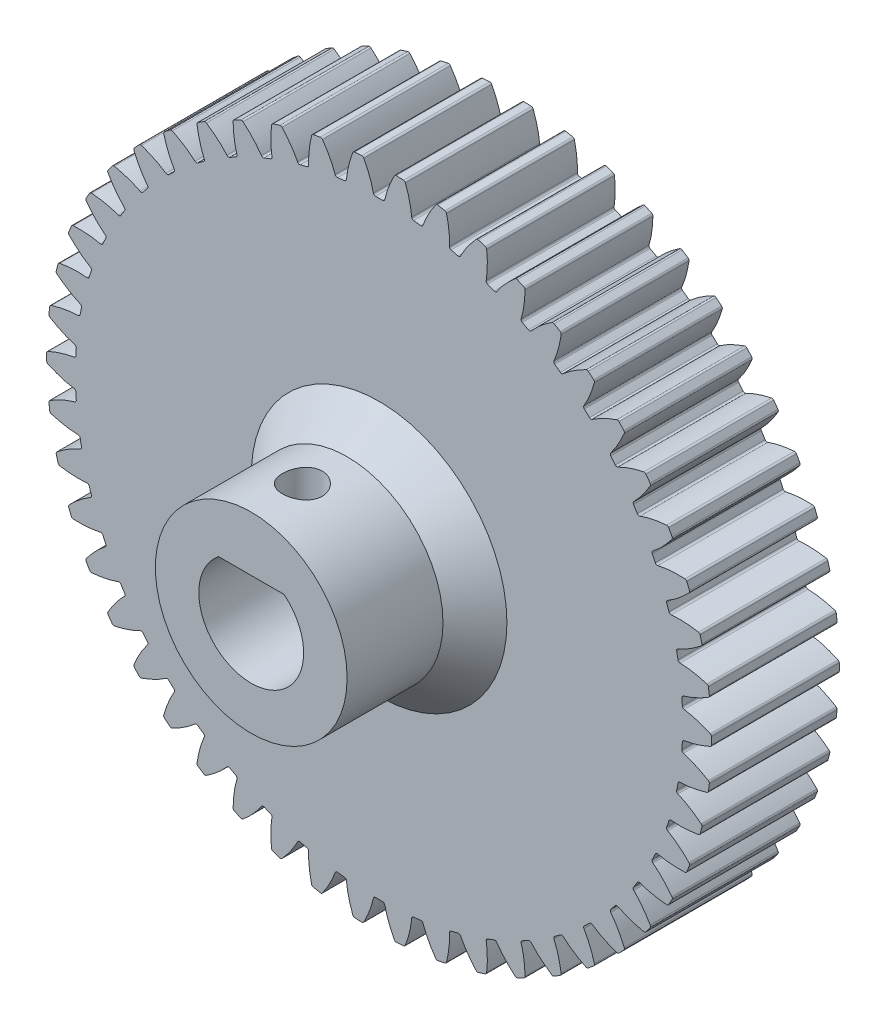
SolidWorks part; units mm, degrees
material "Alloy Steel"
ref_plane "Front" through (0, 0, 0) normal (0, 0, 1) x (1, 0, 0)
ref_plane "Top" through (0, 0, 0) normal (0, 1, 0) x (1, 0, 0)
ref_plane "Right" through (0, 0, 0) normal (1, 0, 0) x (0, 0, -1)
sketch "Sketch1" plane through (0, 0, 0) normal (0, 0, 1) x (1, 0, 0)
  circle A0 centre (0, 0) radius 26
  dimension "OutsideDiameter" = 52
extrude "Boss-Extrude1" add sketch "Sketch1" along normal blind 10
sketch "Sketch3" plane through (0, 0, 0) normal (0, 0, 1) x (1, 0, 0)
  line L0 (0, 0) -> (43.7181, 0) construction
  line L2 (0, 0) -> (-0.3921, 23.7468) construction
  line L3 (0, 0) -> (0.3921, 23.7468) construction
  line L4 (0.3921, 23.7468) -> (0.3879, 23.4891) construction
  line L5 (0, 0) -> (0, 61.276) construction
  line L6 (-0.3921, 23.7468) -> (-0.3879, 23.4891) construction
  circle A0 centre (0, 0) radius 26 construction
  circle A1 centre (0, 0) radius 25 construction
  circle A2 centre (0, 0) radius 23.4923 construction
  arc A3 (0.3921, 23.7468) -> (-0.3921, 23.7468) centre (0, 0) ccw construction
  arc A5 (1.2454, 25.9702) -> (-1.2454, 25.9702) centre (0, 0) ccw
  spline S0 degree 4 poles (-0.3879, 23.4891) (-0.388, 23.493) (-0.3884, 23.504) (-0.3897, 23.5247) (-0.3924, 23.5584) (-0.3969, 23.6014) (-0.4038, 23.6569) (-0.4135, 23.7223) (-0.4257, 23.7941) (-0.4406, 23.8721) (-0.4569, 23.9499) (-0.4746, 24.0275) (-0.4935, 24.1047) (-0.5179, 24.1981) (-0.5491, 24.3101) (-0.5886, 24.4407) (-0.6369, 24.5888) (-0.6899, 24.7394) (-0.7452, 24.8875) (-0.8046, 25.0368) (-0.8646, 25.1811) (-0.9305, 25.3308) (-0.9933, 25.4688) (-1.0677, 25.6231) (-1.1289, 25.7476) (-1.2139, 25.9114) (-1.2654, 26.008) (-1.3272, 26.121) (-1.3555, 26.1712) (-1.3728, 26.202) knots 0 0 0 0 0 0.005377 0.015084 0.028532 0.04661 0.064855 0.092111 0.119476 0.146842 0.174209 0.201575 0.228941 0.256307 0.307035 0.361767 0.4165 0.471232 0.525964 0.580697 0.635429 0.690161 0.744894 0.799626 0.854358 0.909091 0.954545 1 1 1 1 1 construction
  spline S1 degree 4 poles (-0.3879, 23.4891) (-0.388, 23.493) (-0.3884, 23.504) (-0.3897, 23.5247) (-0.3924, 23.5584) (-0.3969, 23.6014) (-0.4038, 23.6569) (-0.4135, 23.7223) (-0.4257, 23.7941) (-0.4406, 23.8721) (-0.4569, 23.9499) (-0.4746, 24.0275) (-0.4935, 24.1047) (-0.5179, 24.1981) (-0.5491, 24.3101) (-0.5886, 24.4407) (-0.6369, 24.5888) (-0.6899, 24.7394) (-0.7452, 24.8875) (-0.8046, 25.0368) (-0.8646, 25.1811) (-0.9305, 25.3308) (-0.9933, 25.4688) (-1.0677, 25.6231) (-1.1289, 25.7476) (-1.1955, 25.8759) (-1.2284, 25.9383) (-1.2454, 25.9702) knots 0 0 0 0 0 0.005377 0.015084 0.028532 0.04661 0.064855 0.092111 0.119476 0.146842 0.174209 0.201575 0.228941 0.256307 0.307035 0.361767 0.4165 0.471232 0.525964 0.580697 0.635429 0.690161 0.744894 0.799626 0.854358 0.909091 0.909091 0.909091 0.909091 0.909091
  spline S2 degree 4 poles (0.3879, 23.4891) (0.388, 23.493) (0.3884, 23.504) (0.3897, 23.5247) (0.3924, 23.5584) (0.3969, 23.6014) (0.4038, 23.6569) (0.4135, 23.7223) (0.4257, 23.7941) (0.4406, 23.8721) (0.4569, 23.9499) (0.4746, 24.0275) (0.4935, 24.1047) (0.5179, 24.1981) (0.5491, 24.3101) (0.5886, 24.4407) (0.6369, 24.5888) (0.6899, 24.7394) (0.7452, 24.8875) (0.8046, 25.0368) (0.8646, 25.1811) (0.9305, 25.3308) (0.9933, 25.4688) (1.0677, 25.6231) (1.1289, 25.7476) (1.2139, 25.9114) (1.2654, 26.008) (1.3272, 26.121) (1.3555, 26.1712) (1.3728, 26.202) knots 0 0 0 0 0 0.005377 0.015084 0.028532 0.04661 0.064855 0.092111 0.119476 0.146842 0.174209 0.201575 0.228941 0.256307 0.307035 0.361767 0.4165 0.471232 0.525964 0.580697 0.635429 0.690161 0.744894 0.799626 0.854358 0.909091 0.954545 1 1 1 1 1 construction
  spline S3 degree 4 poles (0.3879, 23.4891) (0.388, 23.493) (0.3884, 23.504) (0.3897, 23.5247) (0.3924, 23.5584) (0.3969, 23.6014) (0.4038, 23.6569) (0.4135, 23.7223) (0.4257, 23.7941) (0.4406, 23.8721) (0.4569, 23.9499) (0.4746, 24.0275) (0.4935, 24.1047) (0.5179, 24.1981) (0.5491, 24.3101) (0.5886, 24.4407) (0.6369, 24.5888) (0.6899, 24.7394) (0.7452, 24.8875) (0.8046, 25.0368) (0.8646, 25.1811) (0.9305, 25.3308) (0.9933, 25.4688) (1.0677, 25.6231) (1.1289, 25.7476) (1.1955, 25.8759) (1.2284, 25.9383) (1.2454, 25.9702) knots 0 0 0 0 0 0.005377 0.015084 0.028532 0.04661 0.064855 0.092111 0.119476 0.146842 0.174209 0.201575 0.228941 0.256307 0.307035 0.361767 0.4165 0.471232 0.525964 0.580697 0.635429 0.690161 0.744894 0.799626 0.854358 0.909091 0.909091 0.909091 0.909091 0.909091
  point P0 (0, 23.75)
  dimension "OutsideDiameter" = 52
  dimension "PitchCircle" = 50
  dimension "BaseCircle" = 46.9846
  dimension "DedendumCircle" = 47.5
sketch "DCLTBC" [suppressed] plane through (0, 0, 0) normal (0, 0, 1) x (1, 0, 0)
  line L0 (0, 0) -> (41.04, 0) construction
  line L1 (-0.539, 11.2371) -> (-0.5627, 11.7327) construction
  line L2 (0.539, 11.2371) -> (0.5627, 11.7327) construction
  line L3 (-0.539, 11.2371) -> (-0.5627, 11.7327)
  line L4 (0.539, 11.2371) -> (0.5627, 11.7327)
  line L5 (0, 0) -> (0, 104.9356) construction
  circle A0 centre (0, 0) radius 13.5
  circle A1 centre (0, 0) radius 12.5 construction
  circle A2 centre (0, 0) radius 11.7462 construction
  arc A3 (0.539, 11.2371) -> (-0.539, 11.2371) centre (0, 0) ccw construction
  arc A4 (0.539, 11.2371) -> (-0.539, 11.2371) centre (0, 0) ccw
  spline S0 degree 4 poles (-1995.7925, -124.0386) (-18.637, 9.6549) (-0.7482, 10.902) (-0.5144, 11.3546) (-0.568, 11.7819) (-0.5727, 11.8124) (-0.5797, 11.8517) (-0.5892, 11.8979) (-0.601, 11.9485) (-0.6152, 12.0034) (-0.6307, 12.0579) (-0.6473, 12.1122) (-0.6648, 12.1662) (-0.6873, 12.2313) (-0.716, 12.3091) (-0.752, 12.3996) (-0.7958, 12.5017) (-0.8436, 12.6052) (-0.8931, 12.7065) (-0.9461, 12.8082) (-0.9995, 12.9061) (-1.0579, 13.0071) (-1.1133, 13.1) (-1.1787, 13.2033) (-1.5156, 13.7241) (-2.9947, 15.6922) (22.2491, -20.3107) (-1154.5903, 1647.3833) knots -0.784355 -0.784355 -0.784355 -0.784355 -0.784355 0.005377 0.015084 0.028532 0.04661 0.064855 0.092111 0.119476 0.146842 0.174209 0.201575 0.228941 0.256307 0.307035 0.361767 0.4165 0.471232 0.525964 0.580697 0.635429 0.690161 0.744894 0.799626 0.854358 2.062408 2.062408 2.062408 2.062408 2.062408 only from (-0.5627, 11.7327) to (-1.3344, 13.4339) construction
  spline S1 degree 4 poles (1995.7925, -124.0386) (18.637, 9.6549) (0.7482, 10.902) (0.5144, 11.3546) (0.568, 11.7819) (0.5727, 11.8124) (0.5797, 11.8517) (0.5892, 11.8979) (0.601, 11.9485) (0.6152, 12.0034) (0.6307, 12.0579) (0.6473, 12.1122) (0.6648, 12.1662) (0.6873, 12.2313) (0.716, 12.3091) (0.752, 12.3996) (0.7958, 12.5017) (0.8436, 12.6052) (0.8931, 12.7065) (0.9461, 12.8082) (0.9995, 12.9061) (1.0579, 13.0071) (1.1133, 13.1) (1.1787, 13.2033) (1.5156, 13.7241) (2.9947, 15.6922) (-22.2491, -20.3107) (1154.5903, 1647.3833) knots -0.784355 -0.784355 -0.784355 -0.784355 -0.784355 0.005377 0.015084 0.028532 0.04661 0.064855 0.092111 0.119476 0.146842 0.174209 0.201575 0.228941 0.256307 0.307035 0.361767 0.4165 0.471232 0.525964 0.580697 0.635429 0.690161 0.744894 0.799626 0.854358 2.062408 2.062408 2.062408 2.062408 2.062408 only from (0.5627, 11.7327) to (1.3344, 13.4339) construction
  spline S2 degree 4 poles (-0.5627, 11.7327) (-0.5629, 11.7355) (-0.5635, 11.7432) (-0.565, 11.758) (-0.568, 11.7819) (-0.5727, 11.8124) (-0.5797, 11.8517) (-0.5892, 11.8979) (-0.601, 11.9485) (-0.6152, 12.0034) (-0.6307, 12.0579) (-0.6473, 12.1122) (-0.6648, 12.1662) (-0.6873, 12.2313) (-0.716, 12.3091) (-0.752, 12.3996) (-0.7958, 12.5017) (-0.8436, 12.6052) (-0.8931, 12.7065) (-0.9461, 12.8082) (-0.9995, 12.9061) (-1.0579, 13.0071) (-1.1133, 13.1) (-1.1787, 13.2033) (-1.2325, 13.2864) (-1.2907, 13.3715) (-1.3195, 13.4128) (-1.3344, 13.4339) knots 0 0 0 0 0 0.005377 0.015084 0.028532 0.04661 0.064855 0.092111 0.119476 0.146842 0.174209 0.201575 0.228941 0.256307 0.307035 0.361767 0.4165 0.471232 0.525964 0.580697 0.635429 0.690161 0.744894 0.799626 0.854358 0.909091 0.909091 0.909091 0.909091 0.909091
  spline S3 degree 4 poles (0.5627, 11.7327) (0.5629, 11.7355) (0.5635, 11.7432) (0.565, 11.758) (0.568, 11.7819) (0.5727, 11.8124) (0.5797, 11.8517) (0.5892, 11.8979) (0.601, 11.9485) (0.6152, 12.0034) (0.6307, 12.0579) (0.6473, 12.1122) (0.6648, 12.1662) (0.6873, 12.2313) (0.716, 12.3091) (0.752, 12.3996) (0.7958, 12.5017) (0.8436, 12.6052) (0.8931, 12.7065) (0.9461, 12.8082) (0.9995, 12.9061) (1.0579, 13.0071) (1.1133, 13.1) (1.1787, 13.2033) (1.2325, 13.2864) (1.2907, 13.3715) (1.3195, 13.4128) (1.3344, 13.4339) knots 0 0 0 0 0 0.005377 0.015084 0.028532 0.04661 0.064855 0.092111 0.119476 0.146842 0.174209 0.201575 0.228941 0.256307 0.307035 0.361767 0.4165 0.471232 0.525964 0.580697 0.635429 0.690161 0.744894 0.799626 0.854358 0.909091 0.909091 0.909091 0.909091 0.909091
  dimension "OutsideDiameter" = 52
  dimension "PitchCircle" = 50
  dimension "BaseCircle" = 46.9846
extrude "Cut-Extrude-DCLTBC" [suppressed] cut sketch "DCLTBC" along normal through all
fillet "Fillet-Tip-DCLTBC" [suppressed] radius 0.1678
fillet "Fillet-Root-DCLTBC" [suppressed] radius 0.3355
pattern_circular "CirPattern-DCLTBC" [suppressed] count 50 over 360
sketch "DCGTBC" plane through (0, 0, 0) normal (0, 0, 1) x (1, 0, 0)
  line L0 (0, 0) -> (41.04, 0) construction
  line L1 (-23.6596, 2.0699) -> (0, 0) construction
  line L2 (0, 0) -> (23.6596, 2.0699) construction
  line L3 (0, 0) -> (-16.5124, 0)
  line L5 (0, 0) -> (0, 104.9356) construction
  circle A0 centre (0, 0) radius 26
  circle A1 centre (0, 0) radius 25 construction
  circle A2 centre (0, 0) radius 23.4923 construction
  arc A3 (0.3921, 23.7468) -> (-0.3921, 23.7468) centre (0, 0) ccw construction
  arc A11 (23.6596, 2.0699) -> (-23.6596, 2.0699) centre (0, 0) ccw
  spline S4 degree 4 poles (999.4864, -18.7848) (11.7157, 21.9438) (0.5361, 22.5725) (0.3526, 23.0676) (0.3924, 23.5584) (0.3969, 23.6014) (0.4038, 23.6569) (0.4135, 23.7223) (0.4257, 23.7941) (0.4406, 23.8721) (0.4569, 23.9499) (0.4746, 24.0275) (0.4935, 24.1047) (0.5179, 24.1981) (0.5491, 24.3101) (0.5886, 24.4407) (0.6369, 24.5888) (0.6899, 24.7394) (0.7452, 24.8875) (0.8046, 25.0368) (0.8646, 25.1811) (0.9305, 25.3308) (0.9933, 25.4688) (1.0677, 25.6231) (1.3761, 26.2503) (2.5138, 28.2725) (-11.1356, 2.527) (472.7395, 907.8123) knots -0.631302 -0.631302 -0.631302 -0.631302 -0.631302 0.005377 0.015084 0.028532 0.04661 0.064855 0.092111 0.119476 0.146842 0.174209 0.201575 0.228941 0.256307 0.307035 0.361767 0.4165 0.471232 0.525964 0.580697 0.635429 0.690161 0.744894 0.799626 0.854358 1.793522 1.793522 1.793522 1.793522 1.793522 only from (0.3879, 23.4891) to (1.2454, 25.9702) construction
  spline S5 degree 4 poles (-999.4864, -18.7848) (-11.7157, 21.9438) (-0.5361, 22.5725) (-0.3526, 23.0676) (-0.3924, 23.5584) (-0.3969, 23.6014) (-0.4038, 23.6569) (-0.4135, 23.7223) (-0.4257, 23.7941) (-0.4406, 23.8721) (-0.4569, 23.9499) (-0.4746, 24.0275) (-0.4935, 24.1047) (-0.5179, 24.1981) (-0.5491, 24.3101) (-0.5886, 24.4407) (-0.6369, 24.5888) (-0.6899, 24.7394) (-0.7452, 24.8875) (-0.8046, 25.0368) (-0.8646, 25.1811) (-0.9305, 25.3308) (-0.9933, 25.4688) (-1.0677, 25.6231) (-1.3761, 26.2503) (-2.5138, 28.2725) (11.1356, 2.527) (-472.7395, 907.8123) knots -0.631302 -0.631302 -0.631302 -0.631302 -0.631302 0.005377 0.015084 0.028532 0.04661 0.064855 0.092111 0.119476 0.146842 0.174209 0.201575 0.228941 0.256307 0.307035 0.361767 0.4165 0.471232 0.525964 0.580697 0.635429 0.690161 0.744894 0.799626 0.854358 1.793522 1.793522 1.793522 1.793522 1.793522 only from (-0.3879, 23.4891) to (-1.2454, 25.9702) construction
  spline S6 degree 4 poles (0.3879, 23.4891) (0.388, 23.493) (0.3884, 23.504) (0.3897, 23.5247) (0.3924, 23.5584) (0.3969, 23.6014) (0.4038, 23.6569) (0.4135, 23.7223) (0.4257, 23.7941) (0.4406, 23.8721) (0.4569, 23.9499) (0.4746, 24.0275) (0.4935, 24.1047) (0.5179, 24.1981) (0.5491, 24.3101) (0.5886, 24.4407) (0.6369, 24.5888) (0.6899, 24.7394) (0.7452, 24.8875) (0.8046, 25.0368) (0.8646, 25.1811) (0.9305, 25.3308) (0.9933, 25.4688) (1.0677, 25.6231) (1.1289, 25.7476) (1.1955, 25.8759) (1.2284, 25.9383) (1.2454, 25.9702) knots 0 0 0 0 0 0.005377 0.015084 0.028532 0.04661 0.064855 0.092111 0.119476 0.146842 0.174209 0.201575 0.228941 0.256307 0.307035 0.361767 0.4165 0.471232 0.525964 0.580697 0.635429 0.690161 0.744894 0.799626 0.854358 0.909091 0.909091 0.909091 0.909091 0.909091
  spline S7 degree 4 poles (-0.3879, 23.4891) (-0.388, 23.493) (-0.3884, 23.504) (-0.3897, 23.5247) (-0.3924, 23.5584) (-0.3969, 23.6014) (-0.4038, 23.6569) (-0.4135, 23.7223) (-0.4257, 23.7941) (-0.4406, 23.8721) (-0.4569, 23.9499) (-0.4746, 24.0275) (-0.4935, 24.1047) (-0.5179, 24.1981) (-0.5491, 24.3101) (-0.5886, 24.4407) (-0.6369, 24.5888) (-0.6899, 24.7394) (-0.7452, 24.8875) (-0.8046, 25.0368) (-0.8646, 25.1811) (-0.9305, 25.3308) (-0.9933, 25.4688) (-1.0677, 25.6231) (-1.1289, 25.7476) (-1.1955, 25.8759) (-1.2284, 25.9383) (-1.2454, 25.9702) knots 0 0 0 0 0 0.005377 0.015084 0.028532 0.04661 0.064855 0.092111 0.119476 0.146842 0.174209 0.201575 0.228941 0.256307 0.307035 0.361767 0.4165 0.471232 0.525964 0.580697 0.635429 0.690161 0.744894 0.799626 0.854358 0.909091 0.909091 0.909091 0.909091 0.909091
  dimension "D1" = 5
  dimension "D2" = 5
  dimension "OutsideDiameter" = 52
  dimension "PitchCircle" = 50
  dimension "BaseCircle" = 46.9846
extrude "Cut-Extrude-DCGTBC" cut sketch "DCGTBC" along normal through all
fillet "Fillet-Tip-DCGTBC" radius 0.1678 4 edges at (1.2454, 25.9702, 5) (-1.2454, 25.9702, 5) (0.4177, 23.7463, 5) (-0.4177, 23.7463, 5)
pattern_circular "CirPattern-DCGTBC" count 50 over 360 about axis through (0, 0, 10) along (0, 0, 1) of "Cut-Extrude-DCGTBC", "Fillet-Tip-DCGTBC"
sketch "Sketch6" plane through (0, 0, 0) normal (0, 0, -1) x (-1, 0, 0)
  line L0 (-2.5627, 3.2004) -> (2.5627, 3.2004)
  arc A0 (-2.5627, 3.2004) -> (2.5627, 3.2004) centre (0, 0) ccw
  dimension "D1" = 8.2
  dimension "D2" = 3.2004
extrude "Cut-Extrude1" cut sketch "Sketch6" against normal through all both and the other way through all
sketch "Sketch7" plane through (0, 0, 0) normal (0, 0, -1) x (-1, 0, 0)
  circle A0 centre (0, 0) radius 25
  dimension "D1" = 50
sketch "Sketch8" plane through (0, 0, 10) normal (0, 0, 1) x (1, 0, 0)
  circle A0 centre (0, 0) radius 25
  dimension "D1" = 50
sketch "Sketch9" plane through (0, 0, 10) normal (0, 0, 1) x (1, 0, 0)
  line L0 (-2.5627, 3.2004) -> (2.5627, 3.2004) construction
  line L1 (-2.5627, 3.2004) -> (2.5627, 3.2004)
  arc A0 (-2.5627, 3.2004) -> (2.5627, 3.2004) centre (0, 0) ccw construction
  arc A1 (-2.5627, 3.2004) -> (2.5627, 3.2004) centre (0, 0) ccw
  circle A2 centre (0, 0) radius 7.5
  dimension "D1" = 15
extrude "Boss-Extrude3" add sketch "Sketch9" along normal blind 10
chamfer "Chamfer1" distance 2.5 angle 45 1 edges at (7.5, 0, 10)
ref_plane "Plane1" through (0, 7.5, 0) normal (0, 1, 0) x (1, 0, 0)
sketch "Sketch10" plane through (0, 7.5, 0) normal (0, 1, 0) x (1, 0, 0)
  line L0 (-10, -10) -> (10, -10) construction
  line L1 (2.5627, -20) -> (-2.5627, -20) construction
  circle A0 centre (0, -16) radius 1.55
  point P4 (0, 0)
  point P5 (0, -16)
  point P8 (0, -20)
  dimension "D1" = 3.1
  dimension "D2" = 6
extrude "Cut-Extrude2" cut sketch "Sketch10" against normal up to next
equation "\"DiametralPitch\"= 25.4 / 1 'Diametral Pitch"
equation "\"NumTeeth\"= 50'Number of Teeth"
equation "\"PressureAngle\"= 20deg'Pressure Angle"
equation "\"Addendum\"= 1 / \"DiametralPitch\"'Addendum"
equation "\"Dedendum\"= 1.25 / \"DiametralPitch\"'Dedendum"
equation "\"WorkingDepth\"= 2 / \"DiametralPitch\"'Working Depth - here for REF (Not used in building model)"
equation "\"WholeDepth\"= 2.25 / \"DiametralPitch\"'Whole Depth - here for REF (Not used in building model)"
equation "\"Clearance\"= .25 / \"DiametralPitch\"'Clearance"
equation "\"CircularPitch\"= pi / \"DiametralPitch\"'Circular Pitch - here for REF (Not used in building model)"
equation "\"PitchCircle\"= \"NumTeeth\" / \"DiametralPitch\"'Pitch Circle - or - Pitch Diameter"
equation "\"OutsideDiameter\"= ( \"NumTeeth\" + 2 ) / \"DiametralPitch\"'Outside Diameter"
equation "\"Fillet_Root\"= \"Clearance\" * cos ( \"PressureAngle\" ) * tan ( ( 90 + \"PressureAngle\" ) / 2 ) 'Fillet Root"
equation "\"AddendumCircle\"= \"PitchCircle\" + ( 2 * \"Addendum\" )'Addendum Circle - or - Addendum Diameter"
equation "\"DedendumCircle\"= \"PitchCircle\" - ( 2 * \"Dedendum\" )'Dedendum Circle - or - Dedendum Diameter"
equation "\"BaseCircle\"= \"PitchCircle\" * cos ( \"PressureAngle\" )'Base Circle - Base Diameter"
equation "\"PitchAngle\"= 360deg / \"NumTeeth\"'Pitch Angle"
equation "\"Alpha\"= sqr ( \"PitchCircle\" ^ 2 - \"BaseCircle\" ^ 2 ) / \"BaseCircle\" * 180 / PI - \"PressureAngle\"'Alpha - Used for Calculating Beta"
equation "\"Beta\"= ( \"PitchAngle\" / 4 - ( \"Alpha\" - 90 ) )'Beta - Used in definition of the parameters for the parametric equation driven curve"
equation "\"Gamma\"= ( \"PitchAngle\" / 4 - ( \"Alpha\" + 90 ) )'Gamma - Used in definition of the parameters for the parametric equation driven curve"
equation "\"Phi\"= sqr ( ( \"AddendumCircle\" / 2 ) ^ 2 - ( \"BaseCircle\" / 2 ) ^ 2 ) / ( \"BaseCircle\" / 2 )'Phi - Used in definition of the parameters for the parametric equation driven curve"
equation "\"DCGTBC\"= iif ( \"DedendumCircle\" > \"BaseCircle\" , \"unsuppressed\" , \"suppressed\" )'if Dedendum Circle IS GREATER THAN BaseCircle THEN UnsuppressORSuppress FEATURE"
equation "\"DCLTBC\"= iif ( \"DedendumCircle\" - .002 > \"BaseCircle\" , \"suppressed\" , \"unsuppressed\" )'if Dedendum Circle - .002 IS GREATER THAN BaseCircle THEN SuppressORUnsuppress FEATURE"
equation "\"Cut-Extrude-DCGTBC\"= iif ( \"DedendumCircle\" > \"BaseCircle\" , \"unsuppressed\" , \"suppressed\" )'if Dedendum Circle IS GREATER THAN BaseCircle THEN UnsuppressORSuppress FEATURE"
equation "\"Cut-Extrude-DCLTBC\"= iif ( \"DedendumCircle\" - .002 > \"BaseCircle\" , \"suppressed\" , \"unsuppressed\" )'if Dedendum Circle - .002 IS GREATER THAN BaseCircle THEN SuppressORUnsuppress FEATURE"
equation "\"CirPattern-DCGTBC\"= iif ( \"DedendumCircle\" > \"BaseCircle\" , \"unsuppressed\" , \"suppressed\" )'if Dedendum Circle IS GREATER THAN BaseCircle THEN UnsuppressORSuppress FEATURE"
equation "\"CirPattern-DCLTBC\"= iif ( \"DedendumCircle\" - .002 > \"BaseCircle\" , \"suppressed\" , \"unsuppressed\" )'if Dedendum Circle - .002 IS GREATER THAN BaseCircle THEN SuppressORUnsuppress FEATURE"
equation "\"Fillet-Tip-DCGTBC\"= iif ( \"DedendumCircle\" > \"BaseCircle\" , \"unsuppressed\" , \"suppressed\" )'if Dedendum Circle IS GREATER THAN BaseCircle THEN UnsuppressORSuppress FEATURE"
equation "\"Fillet-Tip-DCLTBC\"= iif ( \"DedendumCircle\" - .002 > \"BaseCircle\" , \"suppressed\" , \"unsuppressed\" )'if Dedendum Circle - .002 IS GREATER THAN BaseCircle THEN SuppressORUnsuppress FEATURE"
equation "\"Fillet-Root-DCLTBC\"= iif ( \"DedendumCircle\" - .002 > \"BaseCircle\" , \"suppressed\" , \"unsuppressed\" )'if Dedendum Circle - .002 IS GREATER THAN BaseCircle THEN SuppressORUnsuppress FEATURE"
equation "\"D1@CirPattern-DCGTBC\"= \"NumTeeth\"'Number of Teeth"
equation "\"D1@CirPattern-DCLTBC\"= \"NumTeeth\"'Number of Teeth"
equation "\"D1@Fillet-Tip-DCGTBC\"= \"Fillet_Root\" / 2 'Tip Rad For Large No of Teeth"
equation "\"D1@Fillet-Tip-DCLTBC\"=\"Fillet_Root\" / 2'Tip Rad For Small No of Teeth"
equation "\"D1@Fillet-Root-DCLTBC\"= \"Fillet_Root\"'Fillet Root"
